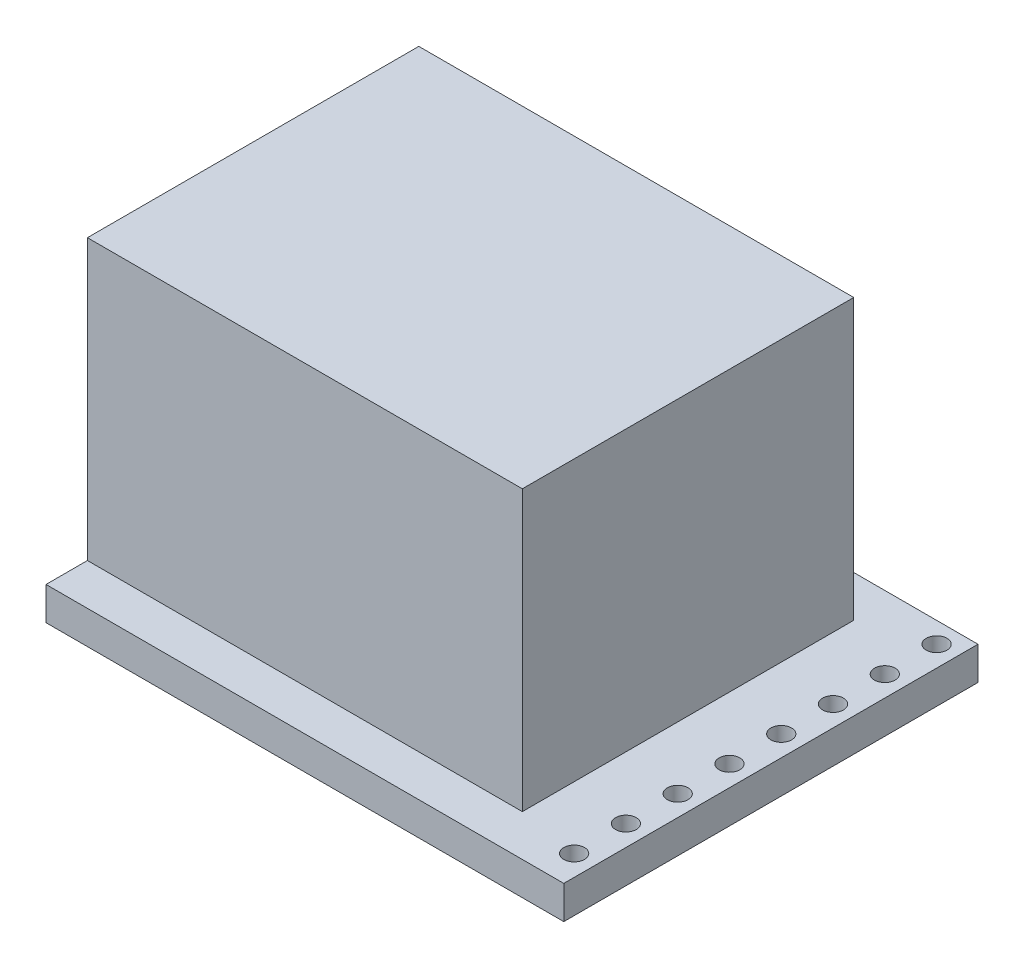
SolidWorks part; units mm, degrees
ref_plane "Front Plane" through (0, 0, 0) normal (0, 0, 1) x (1, 0, 0)
ref_plane "Top Plane" through (0, 0, 0) normal (0, 1, 0) x (1, 0, 0)
ref_plane "Right Plane" through (0, 0, 0) normal (1, 0, 0) x (0, 0, -1)
sketch "Sketch1" plane through (0, 0, 0) normal (0, 1, 0) x (1, 0, 0)
  line L1 (-12.5, -10) -> (12.5, -10)
  line L2 (-12.5, -10) -> (-12.5, 10)
  line L3 (-12.5, 10) -> (12.5, 10)
  line L4 (12.5, -10) -> (12.5, 10)
  line L5 (-12.5, -10) -> (12.5, 10) construction
  line L6 (-12.5, 10) -> (12.5, -10) construction
  point P0 (0, 0)
  dimension "D1" = 20
  dimension "D2" = 25
extrude "Boss-Extrude1" add sketch "Sketch1" against normal blind 1.6
sketch "Sketch2" plane through (0, 0, 0) normal (0, 1, 0) x (1, 0, 0)
  line L0 (-12.5, 10) -> (-12.5, -10) construction
  line L1 (-12.5, 8) -> (8.5, 8)
  line L2 (-12.5, 8) -> (-12.5, -8)
  line L3 (-12.5, -8) -> (8.5, -8)
  line L4 (8.5, 8) -> (8.5, -8)
  point P6 (-12.5, 0)
  point P7 (8.5, 0)
  dimension "D1" = 21
  dimension "D2" = 16
extrude "Boss-Extrude2" add sketch "Sketch2" along normal blind 13.5
sketch "Sketch3" plane through (-12.5, 0, 0) normal (-1, 0, 0) x (0, 0, 1)
  line L0 (-8, 13.5) -> (8, 13.5) construction
  line L1 (-6.2, 3.75) -> (-3.5, 3.75)
  line L2 (-6.2, 3.75) -> (-6.2, 10.75)
  line L3 (-6.2, 10.75) -> (6.2, 10.75)
  line L4 (6.2, 3.75) -> (6.2, 10.75)
  line L5 (-6.2, 3.75) -> (6.2, 10.75) construction
  line L6 (-6.2, 10.75) -> (6.2, 3.75) construction
  line L7 (8, 13.5) -> (8, 0) construction
  line L8 (-8, 13.5) -> (-8, 0) construction
  line L9 (3.5, 3.75) -> (6.2, 3.75)
  line L11 (3.5, 3.75) -> (3.5, 2.25)
  line L12 (3.5, 2.25) -> (-3.5, 2.25)
  line L13 (-3.5, 3.75) -> (-3.5, 2.25)
  point P0 (0, 7.25)
  point P17 (0, 2.25)
  dimension "D1" = 2.75
  dimension "D2" = 1.8
  dimension "D3" = 1.8
  dimension "D4" = 7
  dimension "D5" = 1.5
  dimension "D6" = 7
  dimension "D7" = 2.7
extrude "Cut-Extrude1" cut sketch "Sketch3" against normal blind 13.5
sketch "Sketch4" plane through (0, 0, 0) normal (0, 1, 0) x (1, 0, 0)
  line L0 (12.5, 10) -> (-12.5, 10) construction
  line L1 (12.5, -10) -> (12.5, 10) construction
  line L2 (11.5, 9) -> (11.5, 6.5) construction
  circle A0 centre (11.5, 9) radius 0.5
  circle A1 centre (11.5, 6.5) radius 0.5
  circle A2 centre (11.5, 4) radius 0.5
  circle A3 centre (11.5, 1.5) radius 0.5
  circle A4 centre (11.5, -1) radius 0.5
  circle A5 centre (11.5, -3.5) radius 0.5
  circle A6 centre (11.5, -6) radius 0.5
  circle A7 centre (11.5, -8.5) radius 0.5
  dimension "D2" = 1
  dimension "D1" = 1
  dimension "D3" = 1
  dimension "D5" = 2.5
  dimension "D4" = 8
extrude "Cut-Extrude2" cut sketch "Sketch4" against normal blind 13.5
sketch "Sketch5" plane through (0, -1.6, 0) normal (0, -1, 0) x (-1, 0, 0)
  line L0 (-6.5, -4) -> (-6.5, 4) construction
  line L1 (-8.5, -4) -> (-8.5, 4)
  line L2 (-4.5, -4) -> (-4.5, 4)
  line L3 (-12.5, -10) -> (-12.5, 10) construction
  arc A0 (-8.5, -4) -> (-4.5, -4) centre (-6.5, -4) ccw
  arc A1 (-4.5, 4) -> (-8.5, 4) centre (-6.5, 4) ccw
  point P2 (-6.5, 0)
  point P9 (-12.5, 0)
  dimension "D3" = 8
  dimension "D1" = 6
  dimension "D2" = 4
extrude "Boss-Extrude3" add sketch "Sketch5" along normal blind 2
sketch "Sketch6" plane through (0, -1.6, 0) normal (0, -1, 0) x (1, 0, 0)
  line L0 (-12.5, 10) -> (12.5, 10) construction
  line L1 (12.5, -10) -> (-12.5, -10) construction
  line L2 (-12.5, -10) -> (-12.5, 10) construction
  circle A0 centre (-2.5, 6) radius 1.5
  circle A1 centre (-2.5, -6) radius 1.5
  point P8 (0, 0)
  dimension "D1" = 3
  dimension "D2" = 3
  dimension "D3" = 4
  dimension "D4" = 4
  dimension "D5" = 10
extrude "Boss-Extrude4" add sketch "Sketch6" along normal blind 2
